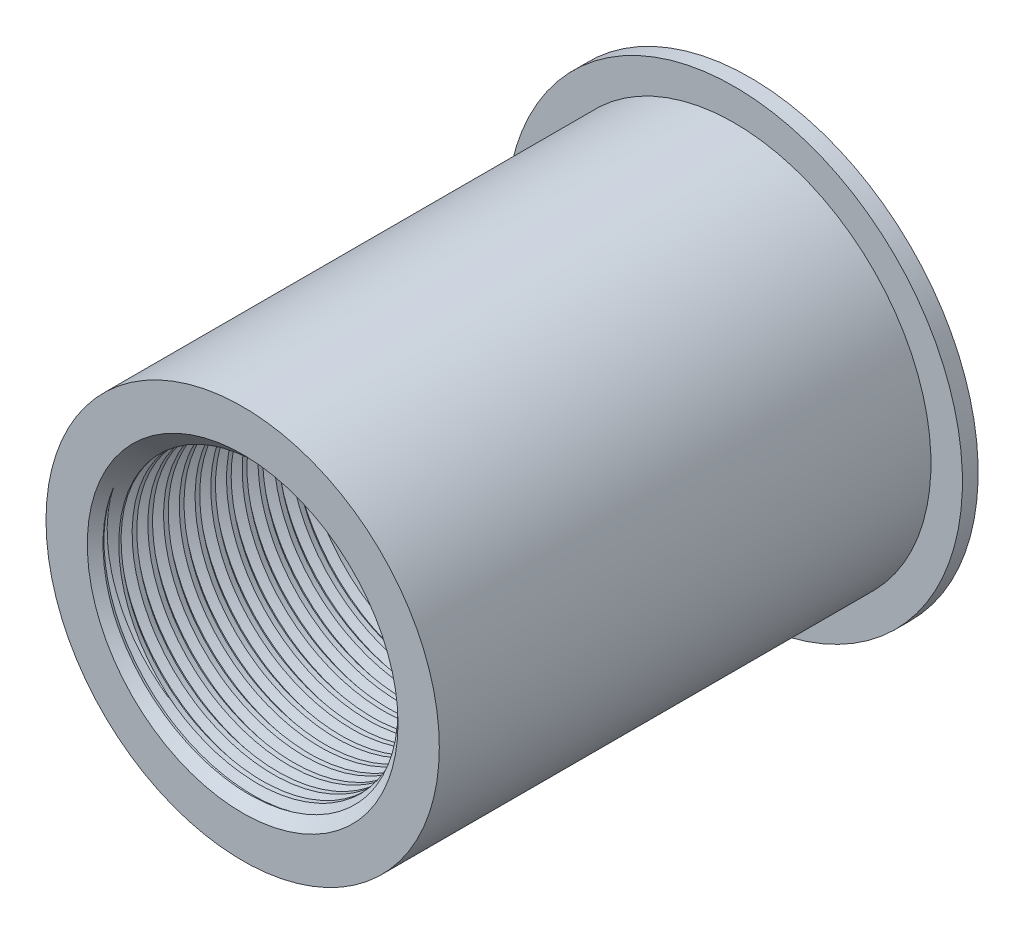
SolidWorks part; units mm, degrees
note: '?' marks a value the reader was unsure of.
ref_plane "Front Plane" through (0, 0, 0) normal (0, 0, 1) x (1, 0, 0)
ref_plane "Top Plane" through (0, 0, 0) normal (0, 1, 0) x (1, 0, 0)
ref_plane "Right Plane" through (0, 0, 0) normal (1, 0, 0) x (0, 0, -1)
sketch "Sketch9" plane through (0, 0, 0) normal (1, 0, 0) x (0, 0, -1)
  line L0 (0, 0) -> (-8.1915, 0) construction
  point P3 (-0.254, 0)
  dimension "flange" = 0.254
  dimension "body" = 7.9375
sketch "Sketch1" plane through (0, 0, 0) normal (0, 0, 1) x (1, 0, 0)
  circle A0 centre (0, 0) radius 3.175
  dimension "c" = 6.35
extrude "Extrude1" add sketch "Sketch1" along normal up to vertex (8.1915 mm away) up to point (0, 0, 8.1915)
sketch "Sketch6" plane through (0, 0, 0) normal (0, 0, -1) x (-1, 0, 0)
  circle A0 centre (0, 0) radius 3.175 construction
  circle A1 centre (0, 0) radius 3.175
  circle A2 centre (0, 0) radius 3.683
  dimension "d" = 7.366
extrude "Extrude2" add sketch "Sketch6" against normal up to vertex (0.254 mm away) up to point (0, 0, 0.254)
sketch "Sketch4" plane through (0, 0, 0) normal (0, 0, -1) x (-1, 0, 0)
  circle A0 centre (0, 0) radius 2.2542
  dimension "D1" = 4.5085
extrude "Cut-Extrude1" cut sketch "Sketch4" against normal through all
sketch "Sketch2" plane through (0, 0, 0) normal (0, 0, 1) x (1, 0, 0)
  circle A0 centre (0, 0) radius 2.3813
  dimension "dec equiv" = 4.7625
curve "Helix/Spiral1" pitch 0.254 height 8.1915 turns 32.25 parameters "pitch"=0.254
sketch "Sketch7" plane through (0, 0, 0) normal (0, 0, -1) x (-1, 0, 0)
  circle A2 centre (0, 0) radius 2.5082
  circle A3 centre (0, 0) radius 2.5082
  dimension "D1" = 0.127
extrude "Cut-Extrude2" cut sketch "Sketch7" against normal through all draft 45
sketch "Sketch8" plane through (0, 0, 8.1915) normal (0, 0, 1) x (1, 0, 0)
  circle A1 centre (0, 0) radius 2.5082
  circle A2 centre (0, 0) radius 2.5082
  dimension "D1" = 0
extrude "Cut-Extrude3" cut sketch "Sketch8" against normal blind 3.175 draft 45
sketch "Sketch3" plane through (0, 0, 0) normal (1, 0, 0) x (0, 0, -1)
  line L0 (-0.0159, 2.3813) -> (0.0159, 2.3813)
  line L1 (-0.0159, 2.3813) -> (-0.1111, 2.2163)
  line L2 (0.0159, 2.3813) -> (0.1111, 2.2163)
  line L3 (0.1111, 2.2163) -> (-0.1111, 2.2163)
  line L4 (0, 2.3813) -> (0, 2.2163) construction
  line L5 (-0.0635, 2.2988) -> (0.0635, 2.2988) construction
  line L6 (0, 2.3813) -> (0, -2.3813) construction
  dimension "D2" = 0.127
  dimension "D3" = 60
sweep "Cut-Sweep1" cut profiles "Sketch3" path "Helix/Spiral1"
ref_plane "Contact Plane 1" through (0, 0, 0) normal (0, 0, -1) x (-1, 0, 0)
ref_axis "Center Axis 1" through (0, 0, 8.1915) along (0, 0, -1)?
equation "\"D1@Sketch3\" = \"pitch@Helix/Spiral1\"*.125"
equation "\"D2@Sketch3\" = \"pitch@Helix/Spiral1\"*.5"
equation "\"D1@Sketch4\"=\"dec equiv@Sketch2\"-\"pitch@Helix/Spiral1\""
equation "\"D3@Helix/Spiral1\"=\"flange@Sketch9\"+\"body@Sketch9\""
